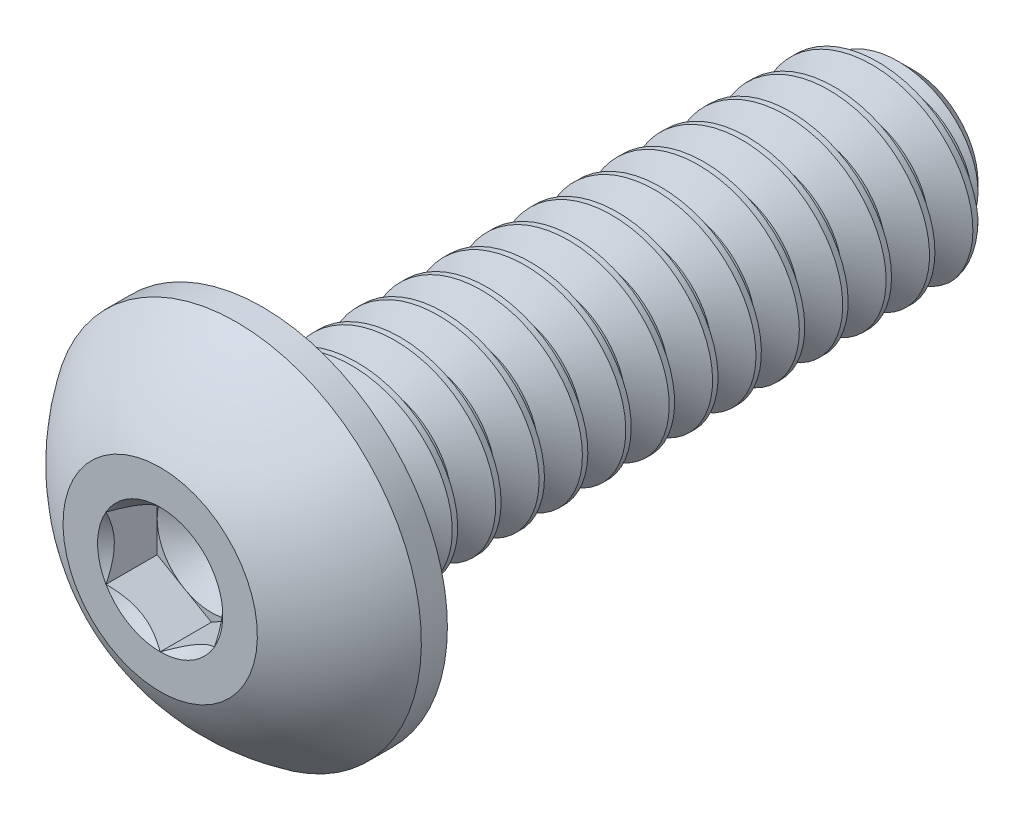
SolidWorks part; units mm, degrees
ref_plane "Front" through (0, 0, 0) normal (0, 0, 1) x (1, 0, 0)
ref_plane "Top" through (0, 0, 0) normal (0, 1, 0) x (1, 0, 0)
ref_plane "Right" through (0, 0, 0) normal (1, 0, 0) x (0, 0, -1)
sketch "Sketch1" plane through (0, 0, 0) normal (1, 0, 0) x (0, 0, -1)
  line L0 (0, 0) -> (-1.4986, 0) construction
  line L1 (0, 0) -> (9.525, 0)
  line L2 (0, 0) -> (0, 1.4224)
  line L3 (0, 1.4224) -> (9.525, 1.4224)
  line L4 (9.525, 0) -> (9.525, 1.4224)
  line L5 (0, -1.4224) -> (9.525, -1.4224) construction
  dimension "D1" = 9.525
  dimension "Thread Dia" = 2.8448
  dimension "Length" = 9.525
  dimension "Head Height" = 1.4986
revolve "Revolve1" add sketch "Sketch1" angle 360 about L0
ref_plane "Plane1" through (0, 0, 1.4986) normal (0, 0, 1) x (1, 0, 0)
chamfer "Chamfer1" distance 0.4763 angle 45 1 edges at (0, 1.4224, -9.525)
sketch "Sketch10" plane through (0, 0, 0) normal (1, 0, 0) x (0, 0, -1)
  line L0 (9.525, 1.4224) -> (10.0806, 1.4224)
  line L1 (10.0806, 1.4224) -> (9.8425, 1.01)
  line L2 (9.8425, 1.01) -> (9.7631, 1.01)
  line L3 (9.7631, 1.01) -> (9.525, 1.4224)
  line L4 (9.6441, 1.2162) -> (9.9616, 1.2162) construction
  dimension "D1" = 60
  dimension "D2" = 0.0794
  dimension "D3" = 0.3175
sketch "Sketch11" plane through (0, 0, -9.525) normal (0, 0, -1) x (-1, 0, 0)
  circle A1 centre (0, 0) radius 0.9462
  circle A2 centre (0, 0) radius 0.9462
  dimension "D1" = 0
curve "Helix/Spiral1" pitch 0.635 height 12.7 turns 20
sweep "Cut-Sweep1" cut profiles "Sketch10" path "Helix/Spiral1"
sketch "Sketch4" plane through (0, 0, 0) normal (0, 0, 1) x (1, 0, 0)
  circle A0 centre (0, 0) radius 2.7051
  dimension "Head Dia" = 5.4102
extrude "Extrude1" add sketch "Sketch4" along normal up to surface (1.4986 mm away) up to plane "Plane1"
sketch "Sketch9" plane through (0, 0, 0) normal (1, 0, 0) x (0, 0, -1)
  line L0 (0, 2.7051) -> (-0.381, 2.7051)
  line L1 (0, 2.7051) -> (0, 3.0861)
  line L2 (0, 3.0861) -> (-1.8796, 3.0861)
  line L3 (0, 0) -> (-1.4986, 0) construction
  line L4 (-1.8796, 3.0861) -> (-1.8796, 1.4224)
  line L5 (-1.8796, 1.4224) -> (-1.4986, 1.4224)
  line L6 (0, 0) -> (0, 1.4224) construction
  line L10 (0, 2.7051) -> (-1.4986, 2.7051) construction
  line L11 (0, 1.4224) -> (9.525, 1.4224) construction
  line L12 (-1.4986, 2.7051) -> (-1.4986, -2.7051) construction
  arc A0 (-1.4986, 1.4224) -> (-0.381, 2.7051) centre (1.4288, 0) cw
  dimension "Side Head Height" = 0.381
revolve "Cut-Revolve3" cut sketch "Sketch9" angle 360 about L3
sketch "Sketch6" plane through (0, 0, 1.4986) normal (0, 0, 1) x (1, 0, 0)
  line L1 (0, -0.9165) -> (0.7937, -0.4583)
  line L2 (0.7937, -0.4583) -> (0.7937, 0.4583)
  line L3 (0.7937, 0.4583) -> (0, 0.9165)
  line L4 (0, 0.9165) -> (-0.7938, 0.4583)
  line L5 (-0.7938, 0.4583) -> (-0.7938, -0.4583)
  line L6 (-0.7938, -0.4583) -> (0, -0.9165)
  circle A0 centre (0, 0) radius 0.7938 construction
  dimension "Hex" = 1.5875
extrude "Cut-Extrude1" cut sketch "Sketch6" against normal blind 0.7493
sketch "Sketch7" plane through (0, 0, 1.4986) normal (0, 0, 1) x (1, 0, 0)
  circle A0 centre (0, 0) radius 0.9165
extrude "Cut-Extrude4" cut sketch "Sketch7" against normal blind 0.7493 draft 45
sketch "Sketch8" plane through (0, 0, 0.7493) normal (0, 0, 1) x (1, 0, 0)
  circle A0 centre (0, 0) radius 0.7938 construction
  circle A1 centre (0, 0) radius 0.7938
extrude "Cut-Extrude5" cut sketch "Sketch8" against normal blind 0.2498 draft 60
sketch "Sketch12" plane through (0, 0, 0) normal (1, 0, 0) x (0, 0, -1)
  line L1 (0, -1.4224) -> (9.525, -1.4224) construction
  spline S0 degree 2 poles (9.0487, 0.013) (9.0069, 0.5945) (8.9694, 1.0058) (8.9165, 1.5865) (8.8635, 1.3739) (8.8106, 1.1614) (8.7577, 0.3681) (8.7048, -0.4251) (8.6519, -1.0058) (8.599, -1.5865) (8.546, -1.3739) (8.4931, -1.1614) (8.4402, -0.3681) (8.3873, 0.4251) (8.3344, 1.0058) (8.2815, 1.5865) (8.2285, 1.3739) (8.1756, 1.1614) (8.1227, 0.3681) (8.0698, -0.4251) (8.0169, -1.0058) (7.964, -1.5865) (7.911, -1.3739) (7.8581, -1.1614) (7.8052, -0.3681) (7.7523, 0.4251) (7.6994, 1.0058) (7.6465, 1.5865) (7.5935, 1.3739) (7.5406, 1.1614) (7.4877, 0.3681) (7.4348, -0.4251) (7.3819, -1.0058) (7.329, -1.5865) (7.276, -1.3739) (7.2231, -1.1614) (7.1702, -0.3681) (7.1173, 0.4251) (7.0644, 1.0058) (7.0115, 1.5865) (6.9585, 1.3739) (6.9056, 1.1614) (6.8527, 0.3681) (6.7998, -0.4251) (6.7469, -1.0058) (6.694, -1.5865) (6.641, -1.3739) (6.5881, -1.1614) (6.5352, -0.3681) (6.4823, 0.4251) (6.4294, 1.0058) (6.3765, 1.5865) (6.3235, 1.3739) (6.2706, 1.1614) (6.2177, 0.3681) (6.1648, -0.4251) (6.1119, -1.0058) (6.059, -1.5865) (6.006, -1.3739) (5.9531, -1.1614) (5.9002, -0.3681) (5.8473, 0.4251) (5.7944, 1.0058) (5.7415, 1.5865) (5.6885, 1.3739) (5.6356, 1.1614) (5.5827, 0.3681) (5.5298, -0.4251) (5.4769, -1.0058) (5.424, -1.5865) (5.371, -1.3739) (5.3181, -1.1614) (5.2652, -0.3681) (5.2123, 0.4251) (5.1594, 1.0058) (5.1065, 1.5865) (5.0535, 1.3739) (5.0006, 1.1614) (4.9477, 0.3681) (4.8948, -0.4251) (4.8419, -1.0058) (4.789, -1.5865) (4.736, -1.3739) (4.6831, -1.1614) (4.6302, -0.3681) (4.5773, 0.4251) (4.5244, 1.0058) (4.4715, 1.5865) (4.4185, 1.3739) (4.3656, 1.1614) (4.3127, 0.3681) (4.2598, -0.4251) (4.2069, -1.0058) (4.154, -1.5865) (4.101, -1.3739) (4.0481, -1.1614) (3.9952, -0.3681) (3.9423, 0.4251) (3.8894, 1.0058) (3.8365, 1.5865) (3.7835, 1.3739) (3.7306, 1.1614) (3.6777, 0.3681) (3.6248, -0.4251) (3.5719, -1.0058) (3.519, -1.5865) (3.466, -1.3739) (3.4131, -1.1614) (3.3602, -0.3681) (3.3073, 0.4251) (3.2544, 1.0058) (3.2015, 1.5865) (3.1485, 1.3739) (3.0956, 1.1614) (3.0427, 0.3681) (2.9898, -0.4251) (2.9369, -1.0058) (2.884, -1.5865) (2.831, -1.3739) (2.7781, -1.1614) (2.7252, -0.3681) (2.6723, 0.4251) (2.6194, 1.0058) (2.5665, 1.5865) (2.5135, 1.3739) (2.4606, 1.1614) (2.4077, 0.3681) (2.3548, -0.4251) (2.3019, -1.0058) (2.249, -1.5865) (2.196, -1.3739) (2.1431, -1.1614) (2.0902, -0.3681) (2.0373, 0.4251) (1.9844, 1.0058) (1.9315, 1.5865) (1.8785, 1.3739) (1.8256, 1.1614) (1.7727, 0.3681) (1.7198, -0.4251) (1.6669, -1.0058) (1.614, -1.5865) (1.561, -1.3739) (1.5081, -1.1614) (1.4552, -0.3681) (1.4023, 0.4251) (1.3494, 1.0058) (1.2965, 1.5865) (1.2435, 1.3739) (1.1906, 1.1614) (1.1377, 0.3681) (1.0848, -0.4251) (1.0319, -1.0058) (0.979, -1.5865) (0.926, -1.3739) (0.8731, -1.1614) (0.8202, -0.3681) (0.7673, 0.4251) (0.7144, 1.0058) (0.6615, 1.5865) (0.6085, 1.3739) (0.5556, 1.1614) (0.5027, 0.3681) (0.4498, -0.4251) (0.3969, -1.0058) (0.344, -1.5865) (0.291, -1.3739) (0.2381, -1.1614) (0.1852, -0.3681) (0.1323, 0.4251) (0.0794, 1.0058) (0.0419, 1.417) (0, 1.4223) knots 0.043858 0.043858 0.043858 0.05 0.05 0.058333 0.058333 0.066667 0.066667 0.075 0.075 0.083333 0.083333 0.091667 0.091667 0.1 0.1 0.108333 0.108333 0.116667 0.116667 0.125 0.125 0.133333 0.133333 0.141667 0.141667 0.15 0.15 0.158333 0.158333 0.166667 0.166667 0.175 0.175 0.183333 0.183333 0.191667 0.191667 0.2 0.2 0.208333 0.208333 0.216667 0.216667 0.225 0.225 0.233333 0.233333 0.241667 0.241667 0.25 0.25 0.258333 0.258333 0.266667 0.266667 0.275 0.275 0.283333 0.283333 0.291667 0.291667 0.3 0.3 0.308333 0.308333 0.316667 0.316667 0.325 0.325 0.333333 0.333333 0.341667 0.341667 0.35 0.35 0.358333 0.358333 0.366667 0.366667 0.375 0.375 0.383333 0.383333 0.391667 0.391667 0.4 0.4 0.408333 0.408333 0.416667 0.416667 0.425 0.425 0.433333 0.433333 0.441667 0.441667 0.45 0.45 0.458333 0.458333 0.466667 0.466667 0.475 0.475 0.483333 0.483333 0.491667 0.491667 0.5 0.5 0.508333 0.508333 0.516667 0.516667 0.525 0.525 0.533333 0.533333 0.541667 0.541667 0.55 0.55 0.558333 0.558333 0.566667 0.566667 0.575 0.575 0.583333 0.583333 0.591667 0.591667 0.6 0.6 0.608333 0.608333 0.616667 0.616667 0.625 0.625 0.633333 0.633333 0.641667 0.641667 0.65 0.65 0.658333 0.658333 0.666667 0.666667 0.675 0.675 0.683333 0.683333 0.691667 0.691667 0.7 0.7 0.708333 0.708333 0.716667 0.716667 0.725 0.725 0.733333 0.733333 0.741667 0.741667 0.75 0.75 0.756142 0.756142 0.756142 weights 0.948065 0.901259 1 0.866025 1 0.866025 1 0.866025 1 0.866025 1 0.866025 1 0.866025 1 0.866025 1 0.866025 1 0.866025 1 0.866025 1 0.866025 1 0.866025 1 0.866025 1 0.866025 1 0.866025 1 0.866025 1 0.866025 1 0.866025 1 0.866025 1 0.866025 1 0.866025 1 0.866025 1 0.866025 1 0.866025 1 0.866025 1 0.866025 1 0.866025 1 0.866025 1 0.866025 1 0.866025 1 0.866025 1 0.866025 1 0.866025 1 0.866025 1 0.866025 1 0.866025 1 0.866025 1 0.866025 1 0.866025 1 0.866025 1 0.866025 1 0.866025 1 0.866025 1 0.866025 1 0.866025 1 0.866025 1 0.866025 1 0.866025 1 0.866025 1 0.866025 1 0.866025 1 0.866025 1 0.866025 1 0.866025 1 0.866025 1 0.866025 1 0.866025 1 0.866025 1 0.866025 1 0.866025 1 0.866025 1 0.866025 1 0.866025 1 0.866025 1 0.866025 1 0.866025 1 0.866025 1 0.866025 1 0.866025 1 0.866025 1 0.866025 1 0.866025 1 0.866025 1 0.866025 1 0.866025 1 0.866025 1 0.866025 1 0.866025 1 0.866025 1 0.866025 1 0.866025 1 0.866025 1 0.866025 1 0.866025 1 0.901259 0.948065 construction
  point P0 (8.5716, -1.4224)
equation "\"D1@Cut-Extrude1\"=\"Head Height@Sketch1\"/2"
equation "\"D1@Cut-Extrude4\"=\"D1@Cut-Extrude1\""
equation "\"D1@Cut-Extrude5\"=\"D1@Cut-Extrude1\"/3"
equation "\"D3@Helix/Spiral1\" = \"Length@Sketch1\" + .125"
equation "\"D1@Chamfer1\" = \"D4@Helix/Spiral1\" * .75"
equation "\"D2@Sketch10\" = \"D4@Helix/Spiral1\" * .125"
equation "\"D3@Sketch10\" = \"D4@Helix/Spiral1\" * .5"
